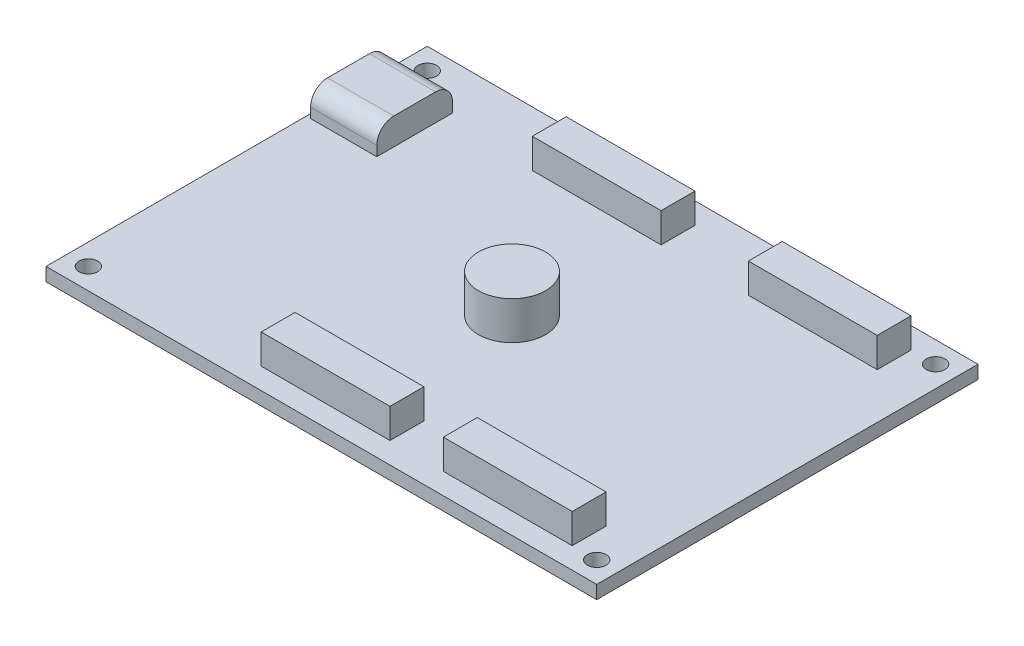
SolidWorks part; units mm, degrees
ref_plane "Front Plane" through (0, 0, 0) normal (0, 0, 1) x (1, 0, 0)
ref_plane "Top Plane" through (0, 0, 0) normal (0, 1, 0) x (1, 0, 0)
ref_plane "Right Plane" through (0, 0, 0) normal (1, 0, 0) x (0, 0, -1)
sketch "Sketch1" plane through (0, 0, 0) normal (0, 1, 0) x (1, 0, 0)
  line L1 (32.5, -22.5) -> (-32.5, -22.5)
  line L2 (32.5, -22.5) -> (32.5, 22.5)
  line L3 (32.5, 22.5) -> (-32.5, 22.5)
  line L4 (-32.5, -22.5) -> (-32.5, 22.5)
  line L5 (32.5, -22.5) -> (-32.5, 22.5) construction
  line L6 (32.5, 22.5) -> (-32.5, -22.5) construction
  line L7 (-9.6, -16) -> (5.6, -16)
  line L8 (-9.6, -16) -> (-9.6, -20)
  line L9 (-9.6, -20) -> (5.6, -20)
  line L10 (5.6, -16) -> (5.6, -20)
  line L11 (11.9, -16) -> (27.1, -16)
  line L12 (11.9, -16) -> (11.9, -20)
  line L13 (11.9, -20) -> (27.1, -20)
  line L14 (27.1, -16) -> (27.1, -20)
  line L15 (-13.6, 20) -> (1.6, 20)
  line L16 (-13.6, 20) -> (-13.6, 16)
  line L17 (-13.6, 16) -> (1.6, 16)
  line L18 (1.6, 20) -> (1.6, 16)
  line L19 (11.9, 20) -> (27.1, 20)
  line L20 (11.9, 20) -> (11.9, 16)
  line L21 (11.9, 16) -> (27.1, 16)
  line L22 (27.1, 20) -> (27.1, 16)
  circle A0 centre (-30, -20) radius 1.1
  circle A1 centre (-30, 20) radius 1.1
  circle A2 centre (30, 20) radius 1.1
  circle A3 centre (30, -20) radius 1.1
  circle A4 centre (0, 0) radius 3.962
  point P0 (0, 0)
  point P30 (19.5, 20)
  point P31 (27.1, 18)
  point P32 (-6, 20)
  point P33 (27.1, -18)
  point P34 (-2, -20)
  dimension "D7" = 2.2
  dimension "D1" = 65
  dimension "D2" = 45
  dimension "D3" = 2.5
  dimension "D4" = 2.5
  dimension "D5" = 2.5
  dimension "D6" = 2.5
  dimension "D8" = 13
  dimension "D9" = 4.5
  dimension "D10" = 4
  dimension "D11" = 15.2
  dimension "D12" = 26.5
  dimension "D13" = 4.5
  dimension "D14" = 30.5
extrude "Boss-Extrude1" add sketch "Sketch1" against normal blind 1.57 contours L4 L1 L2 L3 A4 A3 A2 A1 A0 L7 L10 L9 L8 L11 L14 L13 L12 L15 L18 L17 L16 L19 L22 L21 L20 | L10 L7 L8 L9 | L14 L11 L12 L13 | L18 L15 L16 L17 | A4 | L22 L19 L20 L21 region at (0, 0, 21.7094) region at (-2, 0, 18) region at (19.5, 0, 18) region at (-6, 0, -18) region at (19.5, 0, -18) region at (0, 0, 0)
extrude "Boss-Extrude2" add sketch "Sketch1<4>" along normal blind 3.5 contours L10 L7 L8 L9 | L18 L15 L16 L17 | L22 L19 L20 L21 | L14 L11 L12 L13 region at (-2, 0, 18) region at (19.5, 0, 18) region at (-6, 0, -18) region at (19.5, 0, -18)
sketch "Sketch1<4>" plane through (0, 0, 0) normal (0, 1, 0) x (1, 0, 0) same geometry as "Sketch1"
extrude "Boss-Extrude3" add sketch "Sketch1<5>" along normal blind 4.5 and the other way blind 3.97 contours A4 region at (0, 0, 0)
sketch "Sketch1<5>" plane through (0, 0, 0) normal (0, 1, 0) x (1, 0, 0) same geometry as "Sketch1"
sketch "Sketch2" plane through (0, 0, 0) normal (0, 1, 0) x (1, 0, 0)
  line L0 (-32.5, -22.5) -> (-32.5, 22.5) construction
  line L1 (-32, 17.17) -> (-24.19, 17.17)
  line L2 (-32, 17.17) -> (-32, 8.23)
  line L3 (-32, 8.23) -> (-24.19, 8.23)
  line L4 (-24.19, 17.17) -> (-24.19, 8.23)
  line L5 (32.5, 22.5) -> (-32.5, 22.5) construction
  dimension "D1" = 8.94
  dimension "D2" = 7.81
  dimension "D3" = 0.5
  dimension "D4" = 5.33
extrude "Boss-Extrude4" add sketch "Sketch2" along normal blind 3.16
fillet "Fillet1" radius 2 2 edges at (-28.095, 3.16, -17.17) (-28.095, 3.16, -8.23)
